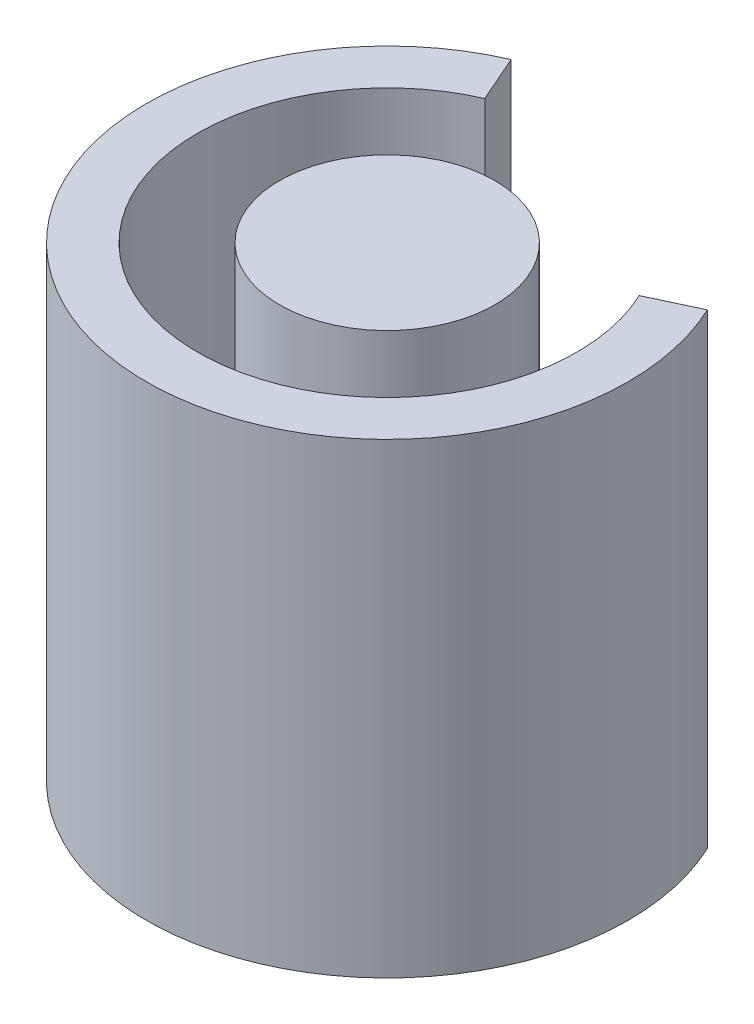
SolidWorks part; units mm, degrees
material "ABS"
ref_plane "Front Plane" through (0, 0, 0) normal (0, 0, 1) x (1, 0, 0)
ref_plane "Top Plane" through (0, 0, 0) normal (0, 1, 0) x (1, 0, 0)
ref_plane "Right Plane" through (0, 0, 0) normal (1, 0, 0) x (0, 0, -1)
sketch "Light sensor area" plane through (0, 0, 0) normal (0, 1, 0) x (1, 0, 0)
  line L0 (-31.73, 25.27) -> (-34.73, 25.27) construction
  line L1 (-34.73, 26.77) -> (-31.73, 26.77) construction
  line L2 (-34.73, 26.77) -> (-34.73, 23.77) construction
  line L3 (-34.73, 23.77) -> (-31.73, 23.77) construction
  line L4 (-31.73, 26.77) -> (-31.73, 23.77) construction
  line L5 (-33.23, 26.77) -> (-33.23, 23.77) construction
  line L7 (-34.73, 27.77) -> (-31.73, 27.77)
  line L8 (-35.73, 26.77) -> (-35.73, 23.77)
  line L9 (-34.73, 22.77) -> (-31.73, 22.77)
  line L10 (-30.73, 26.77) -> (-30.73, 23.77)
  arc A0 (-35.73, 23.77) -> (-34.73, 22.77) centre (-34.73, 23.77) ccw
  arc A1 (-31.73, 22.77) -> (-30.73, 23.77) centre (-31.73, 23.77) ccw
  arc A2 (-31.73, 27.77) -> (-30.73, 26.77) centre (-31.73, 26.77) cw
  arc A3 (-34.73, 27.77) -> (-35.73, 26.77) centre (-34.73, 26.77) ccw
  circle A4 centre (-33.23, 25.27) radius 3.5
  circle A5 centre (-33.23, 25.27) radius 2.3
  point P21 (-30.73, 22.77)
  point P24 (-30.73, 27.77)
sketch "Body outline" plane through (0, 0, 0) normal (0, 0, 1) x (1, 0, 0)
  line L0 (0, 0) -> (-56, 0)
  line L1 (-56, 0) -> (-56, 14)
  line L5 (-54, 2) -> (0, 2)
  line L6 (0, 2) -> (0, 0)
  line L7 (-54, 2) -> (-54, 12.2322)
  line L10 (-52.2322, 14) -> (-54, 12.2322)
  line L12 (-54, 16) -> (-51, 16)
  line L13 (-47.7, 16.4716) -> (-50.1716, 14)
  line L16 (-52.2322, 14) -> (-50.1716, 14)
  line L21 (-54, 29.7678) -> (-52.2322, 28)
  line L22 (-54, 2) -> (-56, 0)
  line L27 (-54, 40.5) -> (-56, 39.7)
  line L32 (0, 0) -> (0, 30.814) construction
  line L33 (-49.55, 28.5) -> (-50.3, 28.5)
  line L34 (-50.8, 28) -> (-50.8, 27)
  line L38 (-56, 39.7) -> (-56, 27.8)
  line L39 (-49.5, 26.5) -> (-49.5, 25.5)
  line L40 (-52.2322, 28) -> (-51, 28)
  line L41 (-51, 28) -> (-51, 26.5)
  line L46 (-51, 26.5) -> (-49.5, 26.5)
  line L47 (-47.7, 16.4716) -> (-47.7, 24.5284)
  line L51 (-49.2, 16) -> (-49.2, 20.5) construction
  line L52 (-50.8, 27) -> (-49.3, 27)
  line L53 (0, 40.5) -> (0, 42.5)
  line L54 (-54, 40.5) -> (0, 40.5)
  line L55 (-47.7, 24.5284) -> (-47.8788, 29)
  line L56 (-53.2, 42.5) -> (0, 42.5)
  line L57 (-51, 25) -> (-50, 25)
  line L58 (-54, 40.5) -> (-54, 29.7678)
  line L59 (-53.2, 25) -> (-51, 25)
  line L60 (-49.3, 27) -> (-49.3, 25)
  line L61 (-49.5, 25.5) -> (-50, 25)
  line L62 (-50.3, 28.5) -> (-50.8, 28)
  line L63 (-50, 25) -> (-49.3, 25)
  line L64 (-49.3, 27) -> (-49.3, 28.5)
  line L66 (-49.3, 28.75) -> (-49.3, 29)
  line L67 (-49.3, 29) -> (-47.8788, 29)
  line L68 (-49.3, 28.75) -> (-49.3, 28.5)
  line L69 (-51, 26.5) -> (-51, 25)
  line L70 (-27, 2) -> (-27, 5.3) construction
  line L71 (0, 41.8) -> (-55.052, 41.8) construction
  arc A0 (-56, 14) -> (-54, 16) centre (-54, 14) cw
  arc A5 (-51, 25) -> (-51, 16) centre (-55.725, 20.5) cw
  arc A7 (-56, 27.8) -> (-53.2, 25) centre (-53.2, 27.8) ccw
  arc A8 (-56, 39.7) -> (-53.2, 42.5) centre (-53.2, 39.7) cw
  arc A9 (-49.3, 28.75) -> (-49.55, 28.5) centre (-49.55, 28.75) cw
  point P20 (-49.5, 25)
  point P22 (-50.8, 28.5)
  point P35 (0, 0)
sketch "Light sensor tube outline" plane through (0, 0, 0) normal (0, 1, 0) x (1, 0, 0)
  arc A0 (-34.7147, 28.6591) -> (-29.8775, 26.8356) centre (-33.23, 25.27) ccw
  circle A1 centre (-33.23, 25.27) radius 2.1
  circle A2 centre (-33.23, 25.27) radius 3.5 construction
  circle A3 centre (-33.23, 25.27) radius 2.3 construction
  dimension "D1" = 0.2
  dimension "D2" = 0.2
extrude "Extrude-Thin light sensor tube" add sketch "Light sensor tube outline" against normal blind 9.1 from vertex thin contours A0 starting at point (0, 40.5, 0) thin type one direction wall 1
extrude "Boss-Extrude light sensor light pipe" add sketch "Light sensor tube outline<3>" against normal blind 8.19 from surface separate body contours A1 starting at face at (-33.4407, 40.5, -24.711)
sketch "Light sensor tube outline<3>" plane through (0, 0, 0) normal (0, 1, 0) x (1, 0, 0) same geometry as "Light sensor tube outline"
equation "\"D1@Light sensor tube outline\"=\"General tolerance@Enclosure master-1.Part\""
equation "\"D5@Extrude-Thin light sensor tube\"=\"Light separator width@Enclosure master-1.Part\""
equation "\"D1@Extrude-Thin light sensor tube\" = \"PCB to inside face@PCB height map@Enclosure master<1>.Part\" - 2 * \"General tolerance@Enclosure master<1>.Part\""
equation "\"D2@Light sensor tube outline\"=\"General tolerance@Enclosure master-1.Part\""
equation "\"D1@Boss-Extrude light sensor light pipe\"=\"PCB to inside face@PCB height map@Enclosure master-1.Part\" - 2 * \"General tolerance@Enclosure master-1.Part\" - \"Light sensor height@PCB height map@Enclosure master-1.Part\""
